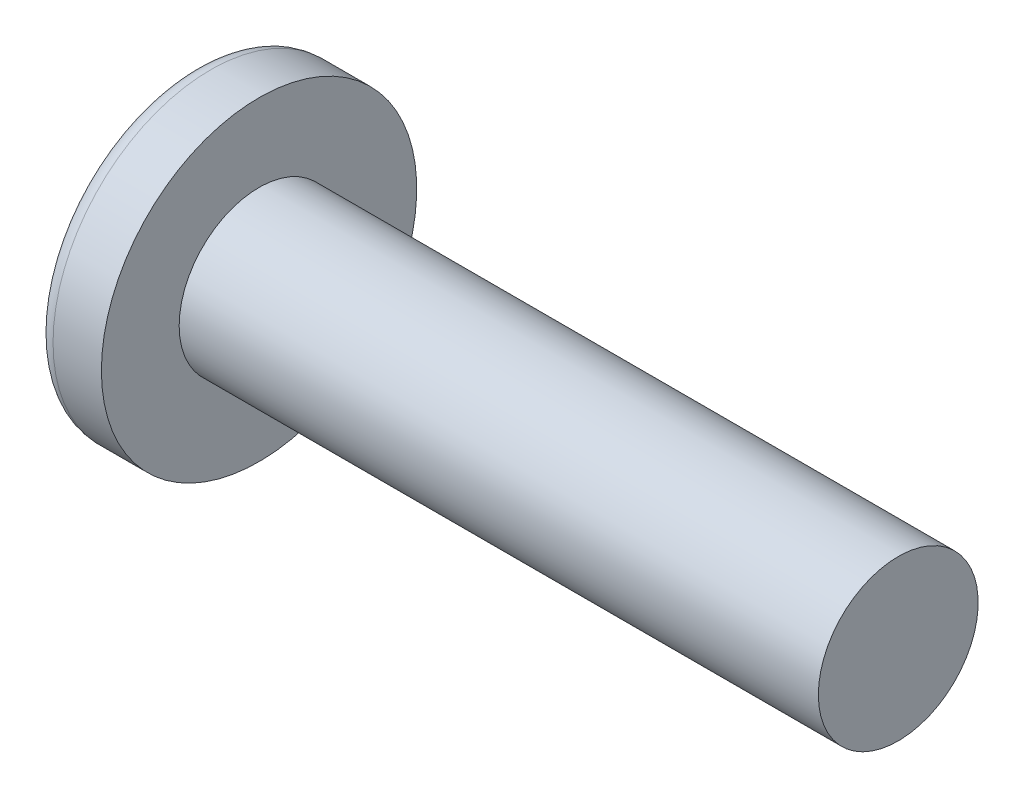
SolidWorks part; units mm, degrees
ref_plane "Plane1" through (0, 0, 0) normal (0, 0, 1) x (1, 0, 0)
ref_plane "Plane2" through (0, 0, 0) normal (0, 1, 0) x (1, 0, 0)
ref_plane "Plane3" through (0, 0, 0) normal (1, 0, 0) x (0, 0, -1)
sketch "BodySke" plane through (0, 0, 0) normal (0, 0, 1) x (1, 0, 0)
  line L0 (6.6294, 4.7625) -> (6.6294, 9.398)
  line L1 (7.4232, 6.35) -> (7.4232, -3.175) construction
  line L2 (-25.4, 0) -> (127, 0) construction
  line L3 (44.7294, 0) -> (0, 0)
  line L4 (6.6294, 4.7625) -> (44.7294, 4.7625)
  line L5 (44.7294, 4.7625) -> (44.7294, 0)
  line L6 (3.7481, 9.398) -> (6.6294, 9.398)
  line L7 (6.6294, -4.7625) -> (44.7294, -4.7625) construction
  line L8 (12.9794, 6.35) -> (12.9794, -3.175) construction
  arc A0 (2.9272, 8.9807) -> (0, 0) centre (15.24, 0) ccw
  arc A2 (2.9272, 8.9807) -> (3.7481, 9.398) centre (3.7481, 8.382) cw
  dimension "Head_fillet_rad" = 1.016
  dimension "Length" = 38.1
  dimension "Head_ht" = 6.6294
  dimension "Head_dia" = 18.796
  dimension "Diameter" = 9.525
  dimension "Advance" = 1.5875
revolve "Base-Revolve" add sketch "BodySke" angle 360 about L2
cosmetic thread "ThreadCosmetic" [suppressed] parameters "Thread_length"=31.75, "Thread_minor"=7.9375
sketch "Sketch3" plane through (0, 0, 0) normal (1, 0, 0) x (0, 0, -1)
  line L0 (1.0287, -6.096) -> (-1.0287, -6.096)
  line L1 (1.0287, -6.096) -> (1.0287, 6.096)
  line L2 (-1.0287, 6.096) -> (1.0287, 6.096)
  line L3 (-1.0287, 6.096) -> (-1.0287, -6.096)
  dimension "D1" = 6.096
  dimension "D2" = 1.0287
ref_plane "Plane4" through (7.2644, 0, 0) normal (1, 0, 0) x (0, 0, -1)
sketch "Sketch4" plane through (7.2644, 0, 0) normal (1, 0, 0) x (0, 0, -1)
  line L0 (0.5143, -0.5143) -> (-0.5143, -0.5144)
  line L1 (0.5143, -0.5143) -> (0.5143, 0.5143)
  line L2 (-0.5143, 0.5143) -> (0.5143, 0.5143)
  line L3 (-0.5143, 0.5143) -> (-0.5143, -0.5144)
  dimension "D2" = 1.0287
  dimension "D1" = 1.0287
  dimension "D3" = 0.5143
  dimension "D4" = 0.5143
loft "Cut-Loft1" cut profiles "Sketch3", "Sketch4"
pattern_circular "CirPattern1" count 2 every 90 about axis through (-25.4, 0, 0) along (1, 0, 0) of "Cut-Loft1"
sketch "ThdSchSke" plane through (0, 0, 0) normal (0, 0, 1) x (1, 0, 0)
  line L0 (12.9794, -3.9688) -> (12.4236, -4.7625)
  line L1 (12.9794, -3.9688) -> (13.5352, -4.7625)
  line L2 (13.5352, -4.7625) -> (13.5352, -5.9531)
  line L3 (-3.175, 0) -> (5.1513, 0) construction
  line L5 (13.5352, -5.9531) -> (12.4236, -5.9531)
  line L6 (12.4236, -5.9531) -> (12.4236, -4.7625)
  dimension "Thread_minor" = 7.9375
  dimension "Diameter" = 9.525
  dimension "Start" = 12.9794
revolve "ThreadSchematic" [suppressed] cut sketch "ThdSchSke" angle 360 about L3
pattern_linear "ThdSchPat" [suppressed]
equation "\"D1@Sketch3\" = \"Cross_dia@Sketch3\" / 2"
equation "\"D2@Sketch3\" = \"Cross_width@Sketch3\" / 2"
equation "\"D1@Sketch4\" = \"Cross_width@Sketch3\" *.5"
equation "\"D2@Sketch4\" = \"D1@Sketch4\""
equation "\"D3@Sketch4\" = \"D1@Sketch4\" / 2"
equation "\"D4@Sketch4\" = \"D2@Sketch4\" / 2"
equation "\"Thread_length@ThreadCosmetic\" = ((sgn( (\"Length@BodySke\" - \"Advance@BodySke\" ) - \"Thread_nom@BodySke\" )-1)*( (\"Length@BodySke\" - \"Advance@BodySke\" ) - \"Thread_nom@BodySke\" ))/-2+ \"Thread_nom@BodySke\""
equation "\"Thread_minor@ThdSchSke\" = \"Thread_minor@ThreadCosmetic\""
equation "\"Diameter@ThdSchSke\" = \"Diameter@BodySke\""
equation "\"Overcut@ThdSchSke\" = \"Diameter@BodySke\" * 1.25"
equation "\"Start@ThdSchSke\" = \"Head_ht@BodySke\" + \"Length@BodySke\" - \"Thread_length@ThreadCosmetic\"  '---Non-countersunk---"
equation "\"Num_threads@ThdSchPat\" = int( \"Thread_length@ThreadCosmetic\" / \"Advance@BodySke\" + 0.999 )  + 1"
equation "\"Advance@ThdSchPat\" = \"Thread_length@ThreadCosmetic\" /  (\"Num_threads@ThdSchPat\" - 1) 'relax it"
